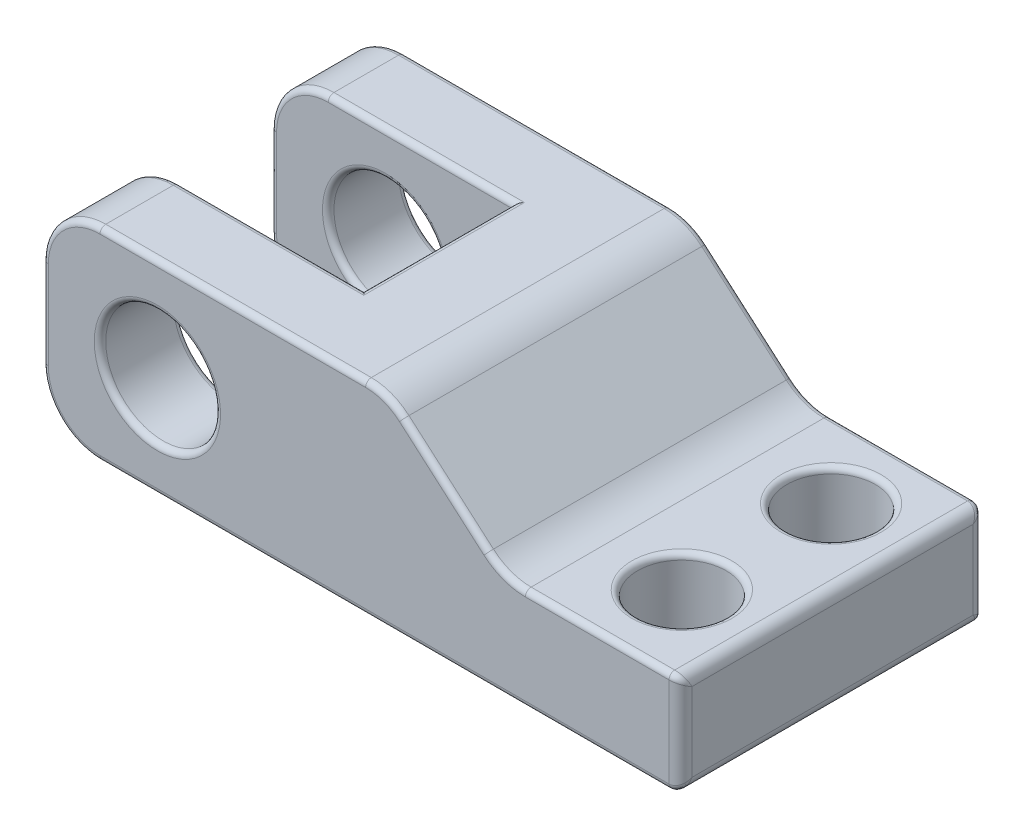
SolidWorks part; units mm, degrees
ref_plane "Front Plane" through (0, 0, 0) normal (0, 0, 1) x (1, 0, 0)
ref_plane "Top Plane" through (0, 0, 0) normal (0, 1, 0) x (1, 0, 0)
ref_plane "Right Plane" through (0, 0, 0) normal (1, 0, 0) x (0, 0, -1)
sketch "Sketch1" plane through (0, 0, 0) normal (0, 0, 1) x (1, 0, 0)
  line L0 (10, 0) -> (30, 0)
  line L2 (30, 35.3914) -> (10, 35.3914)
  line L3 (0, 25.3914) -> (0, 10)
  line L4 (20, 0) -> (20, 35.3914) construction
  line L5 (30, 35.3914) -> (56.2617, 35.3914)
  line L6 (62.8216, 32.9391) -> (77.5388, 20.148)
  line L7 (84.0987, 17.6957) -> (111.1187, 17.6957)
  line L8 (111.1187, 17.6957) -> (111.1187, 0)
  line L9 (111.1187, 0) -> (30, 0)
  circle A0 centre (20, 17.6957) radius 10
  arc A1 (77.5388, 20.148) -> (84.0987, 17.6957) centre (84.0987, 27.6957) ccw
  arc A2 (56.2617, 35.3914) -> (62.8216, 32.9391) centre (56.2617, 25.3914) cw
  arc A3 (10, 0) -> (0, 10) centre (10, 10) cw
  arc A4 (10, 35.3914) -> (0, 25.3914) centre (10, 25.3914) ccw
  point P19 (0, 0)
  dimension "D2" = 10
  dimension "D1" = 30
extrude "Boss-Extrude1" add sketch "Sketch1" along normal blind 53
sketch "Sketch2" plane through (0, 17.6957, 0) normal (0, 1, 0) x (1, 0, 0)
  line L0 (97.6087, -53) -> (97.6087, 0) construction
  line L1 (111.1187, -53) -> (84.0987, -53) construction
  line L2 (111.1187, 0) -> (84.0987, 0) construction
  line L3 (97.6087, -26.5) -> (97.6087, 0) construction
  line L4 (0, -26.5) -> (56.2617, -26.5) construction
  line L5 (0, -53) -> (0, 0) construction
  line L6 (56.2617, -53) -> (56.2617, 0) construction
  line L7 (28.1308, -26.5) -> (28.1308, 0) construction
  line L8 (56.2617, 0) -> (10, 0) construction
  line L9 (28.1308, 0) -> (28.1308, -53) construction
  line L10 (56.2617, -53) -> (10, -53) construction
  line L11 (28.1308, -26.5) -> (28.1308, -13.25) construction
  line L12 (28.1308, -13.25) -> (56.2617, -13.25) construction
  line L13 (28.1308, -39.25) -> (56.2617, -39.25) construction
  line L14 (42.1963, -13.25) -> (0, -13.25)
  line L15 (0, -13.25) -> (0, -39.25)
  line L16 (0, -39.25) -> (42.1963, -39.25)
  line L17 (42.1963, -39.25) -> (42.1963, -13.25)
  circle A0 centre (97.6087, -13.25) radius 7.708
  circle A1 centre (97.6087, -39.25) radius 7.708
  dimension "D1" = 53
  dimension "D2" = 2
extrude "Cut-Extrude1" cut sketch "Sketch2" against normal blind 42 and the other way blind 42
fillet "Fillet1" radius 1 35 edges at (26.0981, 0, 39.25) (2.9289, 2.9289, 39.25) (0, 17.6957, 39.25) (2.9289, 32.4624, 39.25) (26.0981, 0, 13.25) (2.9289, 2.9289, 13.25) (0, 17.6957, 13.25) (2.9289, 32.4624, 13.25) (105.3167, 17.6957, 39.25) (105.3167, 17.6957, 13.25) (26.0981, 35.3914, 39.25) (26.0981, 35.3914, 13.25) (42.1963, 35.3914, 26.25) (97.6087, 17.6957, 0) (80.5971, 18.3288, 0) (70.1802, 26.5435, 0) (59.7633, 34.7583, 0) (60.5593, 0, 0) (2.9289, 2.9289, 0) (0, 17.6957, 0) (2.9289, 32.4624, 0) (97.6087, 17.6957, 53) (80.5971, 18.3288, 53) (70.1802, 26.5435, 53) (59.7633, 34.7583, 53) (60.5593, 0, 53) (2.9289, 2.9289, 53) (0, 17.6957, 53) (2.9289, 32.4624, 53) (10, 17.6957, 39.25) (30, 17.6957, 0) (30, 17.6957, 53) (30, 17.6957, 13.25) (33.1308, 35.3914, 0) (33.1308, 35.3914, 53)
fillet "Fillet2" radius 2 8 edges at (111.1187, 0.2929, 52.7071) (111.1187, 0, 26.5) (111.1187, 0.2929, 0.2929) (111.1187, 17.4028, 0.2929) (111.1187, 17.6957, 26.5) (111.1187, 17.4028, 52.7071) (111.1187, 8.8478, 0) (111.1187, 8.8478, 53)
